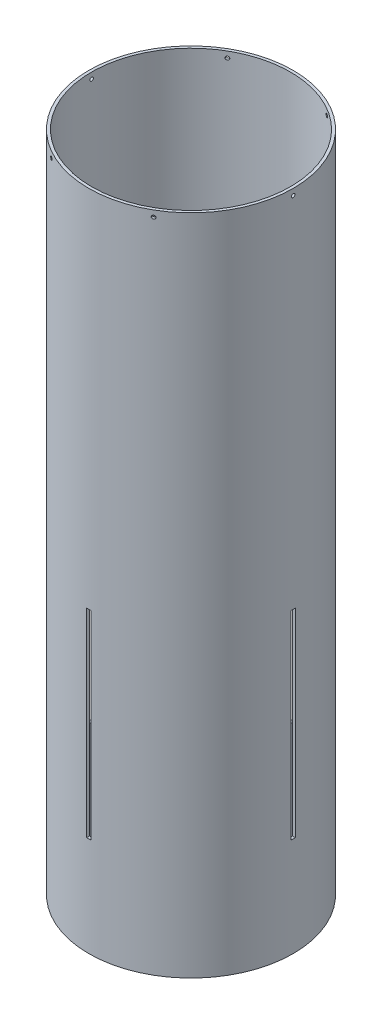
SolidWorks part; units mm, degrees
ref_plane "Front Plane" through (0, 0, 0) normal (0, 0, 1) x (1, 0, 0)
ref_plane "Top Plane" through (0, 0, 0) normal (0, 1, 0) x (1, 0, 0)
ref_plane "Right Plane" through (0, 0, 0) normal (1, 0, 0) x (0, 0, -1)
sketch "Sketch1" plane through (0, 0, 0) normal (0, 1, 0) x (1, 0, 0)
  circle A0 centre (0, 0) radius 76.2
  circle A1 centre (0, 0) radius 78.359
  dimension "D1" = 152.4
  dimension "D2" = 156.718
extrude "Boss-Extrude1" add sketch "Sketch1" along normal blind 508
ref_plane "Plane1" through (0, 0, 0) normal (0.7071, 0, 0.7071) x (0.7071, 0, -0.7071)
ref_axis "Axis1" through (0, 508, 0) along (0, -1, 0)
sketch "Sketch2" plane through (0, 0, 0) normal (1, 0, 0) x (0, 0, -1)
  line L0 (0, 0) -> (0, 76.2)
  line L1 (1.5875, 76.2) -> (-1.5875, 76.2)
  line L2 (1.5875, 76.2) -> (1.5875, 228.6)
  line L3 (1.5875, 228.6) -> (-1.5875, 228.6)
  line L4 (-1.5875, 76.2) -> (-1.5875, 228.6)
  line L5 (1.5875, 76.2) -> (-1.5875, 228.6) construction
  line L6 (1.5875, 228.6) -> (-1.5875, 76.2) construction
  line L7 (78.359, 508) -> (-78.359, 508) construction
  line L8 (78.359, 508) -> (-78.359, 508)
  line L9 (0, 508) -> (0, 503.2375)
  circle A0 centre (0, 503.2375) radius 1.3525
  point P0 (0, 152.4)
  dimension "D4" = 2.7051
  dimension "D1" = 3.175
  dimension "D2" = 152.4
  dimension "D3" = 76.2
  dimension "D5" = 4.7625
extrude "Cut-Extrude1" cut sketch "Sketch2" against normal through all contours L4 L1 L2 L3 region at (0, 152.4, 0)
pattern_circular "CirPattern1" count 4 over 360 about axis through (0, 0, 0) along (0, 1, 0) of "Cut-Extrude1" reverse direction yes
extrude "Cut-Extrude2" cut sketch "Sketch2<3>" against normal through all contours A0 region at (0, 502.3082, 0.9293)
sketch "Sketch2<3>" plane through (0, 0, 0) normal (1, 0, 0) x (0, 0, -1) same geometry as "Sketch2"
pattern_circular "CirPattern2" count 6 over 360 about axis through (0, 508, 0) along (0, -1, 0) of "Cut-Extrude2"
sketch "Sketch3" plane through (0, 0, 0) normal (0.7071, 0, 0.7071) x (0.7071, 0, -0.7071)
  line L0 (0, 0) -> (0, 127) construction
  circle A0 centre (0, 127) radius 3.175
  dimension "D1" = 6.35
  dimension "D2" = 127
extrude "Cut-Extrude3" cut sketch "Sketch3" against normal through all
equation "\"Aft_Lower_Length\"= 20in"
equation "\"D1@Boss-Extrude1\"=\"Aft_Lower_Length\""
equation "\"AB_Coupler_OD_Length\"= 2in"
equation "\"AB_Coupling_Section_Length\"= 0.375in"
equation "\"AB_Coupler_Length\"= \"AB_Coupler_OD_Length\" + \"AB_Coupling_Section_Length\" * 2"
equation "\"AB_Coupler_Num_Screws\"= 6"
equation "\"AB_Coupling_Screw_Diameter\"= 0.1065in"
equation "\"Aft_Upper_Length\"= \"Aft_Section_Length\" - \"Aft_Lower_Length\" - \"AB_Coupler_OD_Length\""
equation "\"Aft_Section_Length\"= 40in"
equation "\"D4@Sketch2\"=\"AB_Coupling_Screw_Diameter\""
equation "\"D5@Sketch2\"=\"AB_Coupling_Section_Length\"/2"
equation "\"D1@CirPattern2\"=\"AB_Coupler_Num_Screws\""
equation "\"Rail_Nut_From_Bottom\"= 5in"
equation "\"Rail_Nut_Diam\"= 0.25in"
equation "\"D1@Sketch3\"=\"Rail_Nut_Diam\""
equation "\"D2@Sketch3\"=\"Rail_Nut_From_Bottom\""
